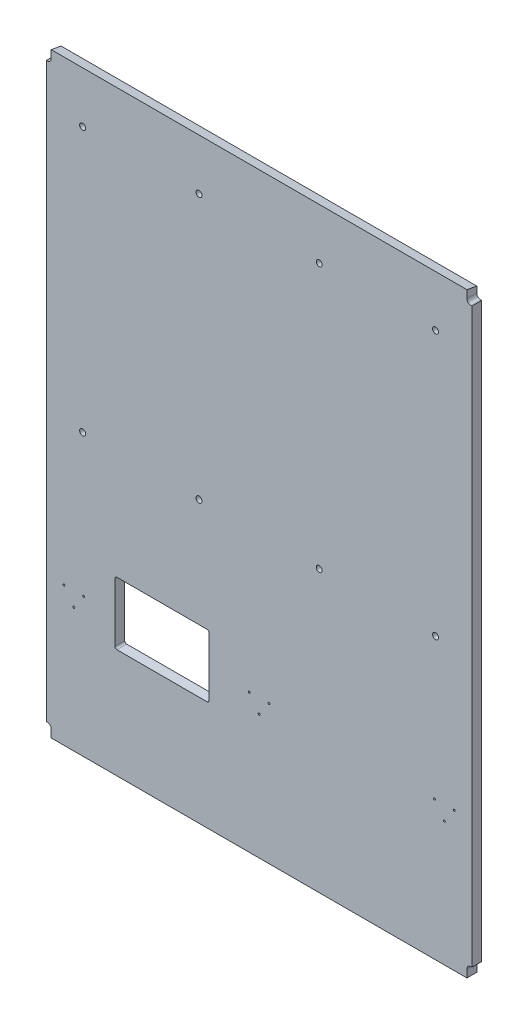
SolidWorks part; units mm, degrees
ref_plane "Front Plane" through (0, 0, 0) normal (0, 0, 1) x (1, 0, 0)
ref_plane "Top Plane" through (0, 0, 0) normal (0, 1, 0) x (1, 0, 0)
ref_plane "Right Plane" through (0, 0, 0) normal (1, 0, 0) x (0, 0, -1)
sketch "Sketch1" plane through (0, 0, 0) normal (0, 0, 1) x (1, 0, 0)
  line L1 (336.55, 482.6) -> (-336.55, 482.6)
  line L2 (336.55, 482.6) -> (336.55, -482.6)
  line L3 (336.55, -482.6) -> (-336.55, -482.6)
  line L4 (-336.55, 482.6) -> (-336.55, -482.6)
  line L5 (336.55, 482.6) -> (-336.55, -482.6) construction
  line L6 (336.55, -482.6) -> (-336.55, 482.6) construction
  point P0 (0, 0)
  dimension "D1" = 673.1
  dimension "D2" = 965.2
extrude "Boss-Extrude1" add sketch "Sketch1" along normal mid plane 15.875
sketch "Sketch2" plane through (0, 0, 7.9375) normal (0, 0, 1) x (1, 0, 0)
  line L2 (-336.55, 482.6) -> (-336.55, -482.6) construction
  line L3 (-230.3281, -204.0862) -> (-84.2781, -204.0862)
  line L4 (-233.5031, -207.2612) -> (-233.5031, -302.5112)
  line L5 (-230.3281, -305.6862) -> (-84.2781, -305.6862)
  line L6 (-81.1031, -207.2612) -> (-81.1031, -302.5112)
  line L7 (-336.55, -482.6) -> (336.55, -482.6) construction
  arc A1 (-84.2781, -204.0862) -> (-81.1031, -207.2612) centre (-84.2781, -207.2612) cw
  arc A2 (-84.2781, -305.6862) -> (-81.1031, -302.5112) centre (-84.2781, -302.5112) ccw
  arc A3 (-233.5031, -302.5112) -> (-230.3281, -305.6862) centre (-230.3281, -302.5112) ccw
  arc A4 (-230.3281, -204.0862) -> (-233.5031, -207.2612) centre (-230.3281, -207.2612) ccw
  point P6 (-81.1031, -204.0862)
  point P11 (-233.5031, -305.6862)
  point P14 (-233.5031, -204.0862)
  dimension "D1" = 101.6
  dimension "D3" = 3.175
  dimension "D2" = 152.4
  dimension "D4" = 103.0469
  dimension "D5" = 176.9138
extrude "Cut-Extrude1" cut sketch "Sketch2" against normal through all both and the other way through all
sketch "Sketch3" plane through (336.55, 0, 0) normal (1, 0, 0) x (0, 0, -1)
  line L0 (-7.9375, 482.6) -> (7.9375, 479.8008)
  line L1 (7.9375, -482.6) -> (7.9375, 482.6) construction
  line L2 (7.9375, 479.8008) -> (7.9375, 482.6)
  line L3 (7.9375, 482.6) -> (-7.9375, 482.6)
  dimension "D1" = 10
extrude "Cut-Extrude2" cut sketch "Sketch3" against normal through all
sketch "Sketch4" plane through (0, 0, 7.9375) normal (0, 0, 1) x (1, 0, 0)
  line L0 (-336.55, 482.6) -> (-336.55, -482.6) construction
  line L1 (-336.55, 463.55) -> (-344.4875, 463.55)
  line L2 (-336.55, 463.55) -> (-336.55, -463.55)
  line L3 (-336.55, -463.55) -> (-344.4875, -463.55)
  line L4 (-344.4875, 463.55) -> (-344.4875, -463.55)
  line L5 (336.55, -482.6) -> (336.55, 482.6) construction
  line L6 (336.55, 463.55) -> (344.4875, 463.55)
  line L7 (336.55, 463.55) -> (336.55, -463.55)
  line L8 (336.55, -463.55) -> (344.4875, -463.55)
  line L9 (344.4875, 463.55) -> (344.4875, -463.55)
  line L10 (0, 0) -> (0, 87.9986) construction
  line L12 (0, 0) -> (-174.9175, 0) construction
  line L13 (-336.55, -482.6) -> (336.55, -482.6) construction
  dimension "D1" = 19.05
  dimension "D2" = 7.9375
  dimension "D3" = 688.975
extrude "Boss-Extrude2" add sketch "Sketch4" against normal up to surface (15.875 mm away) up to face at (0, -1.3996, -7.9375)
fillet "Fillet1" radius 6.35 4 edges at (336.55, -463.55, 0) (-336.55, -463.55, 0) (-336.55, 463.55, 0) (336.55, 463.55, 0)
sketch "Sketch5" plane through (0, 0, 7.9375) normal (0, 0, 1) x (1, 0, 0)
  line L0 (-301.5961, -297.8717) -> (-145.6989, -297.8717) construction
  line L1 (-300, -280.8717) -> (-300, -246.7738) construction
  line L2 (0, 0) -> (0, -280.8717) construction
  line L3 (-300, -309.3289) -> (-300, -255.3083) construction
  line L4 (-336.55, -482.6) -> (336.55, -482.6) construction
  circle A0 centre (-316, -257.8717) radius 1.5875
  circle A1 centre (-284, -257.8717) radius 1.5875
  circle A2 centre (-300, -280.8717) radius 1.5875
  circle A6 centre (-16, -257.8717) radius 1.5875
  circle A7 centre (16, -257.8717) radius 1.5875
  circle A8 centre (0, -280.8717) radius 1.5875
  circle A9 centre (284, -257.8717) radius 1.5875
  circle A10 centre (300, -280.8717) radius 1.5875
  circle A11 centre (316, -257.8717) radius 1.5875
  dimension "D1" = 3.175
  dimension "D2" = 17
  dimension "D3" = 23
  dimension "D4" = 32
  dimension "D5" = 32
  dimension "D6" = 201.7283
  dimension "D7" = 300
extrude "Cut-Extrude3" cut sketch "Sketch5" against normal blind 8
sketch "Sketch6" plane through (0, 0, -7.9375) normal (0, 0, -1) x (-1, 0, 0)
  line L0 (0, 0) -> (0, 482.6) construction
  circle A0 centre (-285.75, 400.05) radius 4.826
  circle A1 centre (-97.3667, 400.05) radius 4.826
  circle A2 centre (97.3667, 400.05) radius 4.826
  circle A3 centre (285.75, 400.05) radius 4.826
  circle A4 centre (-285.75, -28.575) radius 4.826
  circle A5 centre (-97.3667, -28.575) radius 4.826
  circle A6 centre (97.3667, -28.575) radius 4.826
  circle A7 centre (285.75, -28.575) radius 4.826
  dimension "D1" = 571.5
  dimension "D2" = 194.7333
  dimension "D3" = 28.575
  dimension "D4" = 9.652
  dimension "D5" = 428.625
extrude "Cut-Extrude4" cut sketch "Sketch6" against normal through all
